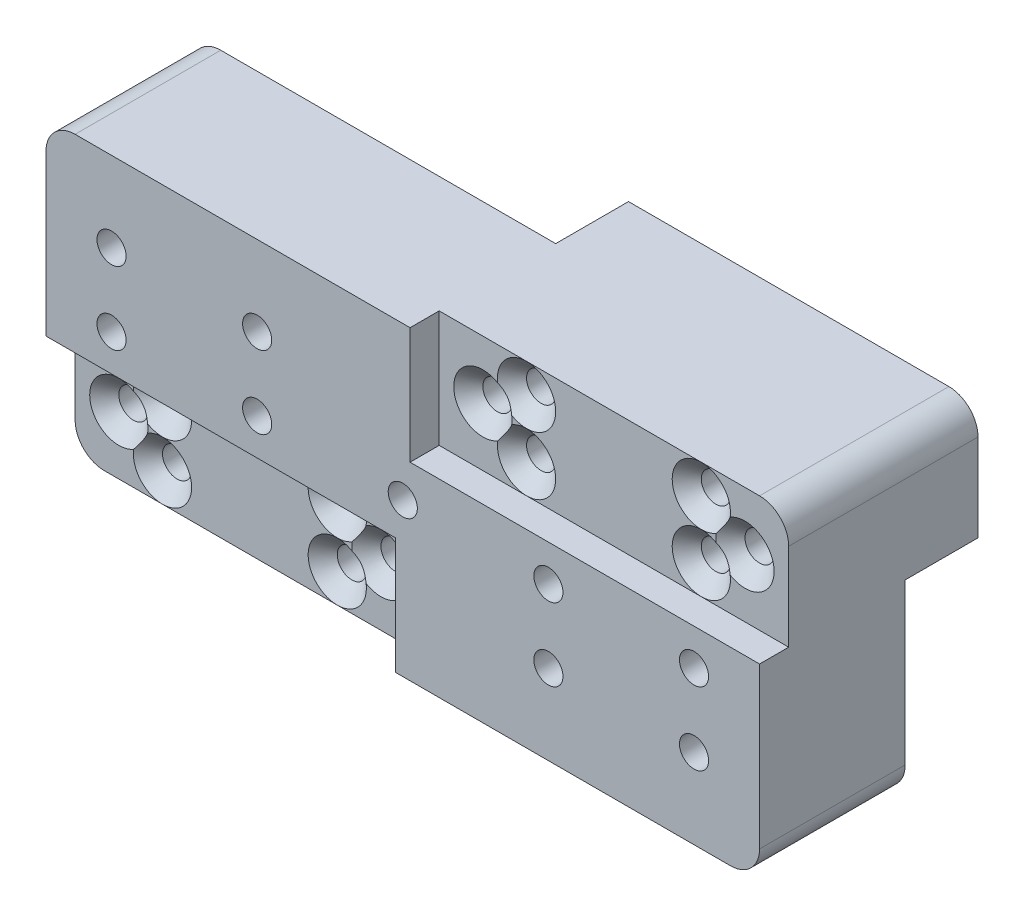
SolidWorks part; units mm, degrees
ref_plane "Front Plane" through (0, 0, 0) normal (0, 0, 1) x (1, 0, 0)
ref_plane "Top Plane" through (0, 0, 0) normal (0, 1, 0) x (1, 0, 0)
ref_plane "Right Plane" through (0, 0, 0) normal (1, 0, 0) x (0, 0, -1)
sketch "Sketch1" plane through (0, 0, 0) normal (0, 0, 1) x (1, 0, 0)
  line L0 (16.5, 10.5204) -> (16.5, 2.5204) construction
  line L1 (-20.5, -2.4796) -> (3.5, -2.4796)
  line L2 (-20.5, -2.4796) -> (-20.5, -10.4796)
  line L3 (-20.5, -10.4796) -> (3.5, -10.4796)
  line L4 (3.5, -2.4796) -> (3.5, -10.4796)
  line L5 (4.5, 10.5204) -> (28.5, 10.5204)
  line L6 (4.5, 10.5204) -> (4.5, 2.5204)
  line L7 (4.5, 2.5204) -> (28.5, 2.5204)
  line L8 (28.5, 10.5204) -> (28.5, 2.5204)
  line L9 (16.5, 6.5204) -> (4.5, 6.5204) construction
  line L10 (-8.5, -10.4796) -> (-8.5, -2.4796) construction
  line L11 (-8.5, -6.4796) -> (3.5, -6.4796) construction
  circle A0 centre (10.5, 8.5204) radius 1
  circle A1 centre (7.5, 6.5204) radius 1
  circle A2 centre (10.5, 4.5204) radius 1
  circle A3 centre (22.5, 4.5204) radius 1
  circle A4 centre (25.5, 6.5204) radius 1
  circle A5 centre (22.5, 8.5204) radius 1
  circle A6 centre (0.5, -6.4796) radius 1
  circle A7 centre (-14.5, -4.4796) radius 1
  circle A8 centre (-2.5, -8.4796) radius 1
  circle A10 centre (-17.5, -6.4796) radius 1
  circle A11 centre (-14.5, -8.4796) radius 1
  circle A12 centre (-2.5, -4.4796) radius 1
  dimension "D7" = 2
  dimension "D8" = 9
  dimension "D15" = 2
  dimension "D16" = 2
  dimension "D17" = 2
  dimension "D1" = 8
  dimension "D2" = 8
  dimension "D3" = 1
  dimension "D4" = 24
  dimension "D5" = 24
  dimension "D6" = 5
  dimension "D9" = 6
  dimension "D10" = 2
  dimension "D11" = 9
  dimension "D13" = 2
extrude "Boss-Extrude1" add sketch "Sketch1" along normal blind 5
sketch "Sketch2" plane through (0, 0, 5) normal (0, 0, 1) x (1, 0, 0)
  line L1 (-20.5, -10.4796) -> (28.5, -10.4796)
  line L2 (-20.5, -10.4796) -> (-20.5, 10.5204)
  line L3 (-20.5, 10.5204) -> (28.5, 10.5204)
  line L4 (-20.5, -2.4796) -> (-20.5, -10.4796)
  line L5 (-20.5, -10.4796) -> (3.5, -10.4796)
  line L6 (3.5, -10.4796) -> (3.5, -2.4796)
  line L7 (3.5, -2.4796) -> (-20.5, -2.4796)
  line L8 (-20.5, -2.4796) -> (-20.5, -10.4796)
  line L9 (-20.5, -10.4796) -> (3.5, -10.4796)
  line L10 (3.5, -10.4796) -> (3.5, -2.4796)
  line L11 (3.5, -2.4796) -> (-20.5, -2.4796)
  line L12 (4.5, 10.5204) -> (4.5, 2.5204)
  line L13 (4.5, 2.5204) -> (28.5, 2.5204)
  line L14 (28.5, 2.5204) -> (28.5, 10.5204)
  line L15 (28.5, 10.5204) -> (4.5, 10.5204)
  line L16 (4.5, 10.5204) -> (4.5, 2.5204)
  line L17 (4.5, 2.5204) -> (28.5, 2.5204)
  line L18 (28.5, 2.5204) -> (28.5, 10.5204)
  line L19 (28.5, 10.5204) -> (4.5, 10.5204)
  line L20 (28.5, -10.4796) -> (28.5, 10.5204)
  circle A0 centre (-14.5, -8.4796) radius 1 construction
  circle A1 centre (-17.5, -6.4796) radius 1 construction
  circle A2 centre (-14.5, -4.4796) radius 1 construction
  circle A3 centre (-2.5, -8.4796) radius 1 construction
  circle A5 centre (0.5, -6.4796) radius 1 construction
  circle A6 centre (7.5, 6.5204) radius 1 construction
  circle A7 centre (10.5, 8.5204) radius 1 construction
  circle A8 centre (10.5, 4.5204) radius 1 construction
  circle A9 centre (22.5, 8.5204) radius 1 construction
  circle A10 centre (25.5, 6.5204) radius 1 construction
  circle A11 centre (22.5, 4.5204) radius 1 construction
  circle A12 centre (22.5, 4.5204) radius 1
  circle A13 centre (25.5, 6.5204) radius 1
  circle A14 centre (22.5, 8.5204) radius 1
  circle A15 centre (10.5, 4.5204) radius 1
  circle A16 centre (10.5, 8.5204) radius 1
  circle A17 centre (7.5, 6.5204) radius 1
  circle A18 centre (0.5, -6.4796) radius 1
  circle A20 centre (-2.5, -8.4796) radius 1
  circle A21 centre (-14.5, -4.4796) radius 1
  circle A22 centre (-17.5, -6.4796) radius 1
  circle A23 centre (-14.5, -8.4796) radius 1
  circle A24 centre (-2.5, -4.4796) radius 1 construction
  circle A25 centre (-2.5, -4.4796) radius 1
  circle M9 centre (0.5, -6.4796) radius 1
  circle M10 centre (-14.5, -8.4796) radius 1
  circle M11 centre (-14.5, -4.4796) radius 1
  line M12 (-20.5, -2.4796) -> (-20.5, -10.4796)
  line M13 (-20.5, -10.4796) -> (3.5, -10.4796)
  line M14 (3.5, -10.4796) -> (3.5, -2.4796)
  line M15 (3.5, -2.4796) -> (-20.5, -2.4796)
  circle M16 centre (-17.5, -6.4796) radius 1
  circle M17 centre (-2.5, -8.4796) radius 1
  dimension "D1" = 0
  dimension "D2" = 0
extrude "Boss-Extrude2" add sketch "Sketch2" along normal blind 8 contours L1 L20 L17 L16 L3 L2 M15 M14 | L17 L18 L3 L16 A17 A16 A15 A14 A13 A12 | M15 M12 M13 M14 M10 M17 M16 M11 M9 region at (-8.5, -6.4796, 5) region at (4, 0.0204, 5) region at (16.5, 6.5204, 5)
extrude "Boss-Extrude3" add sketch "Sketch2<6>" along normal blind 10 contours L1 L20 L17 L16 L3 L2 M15 M14 region at (4, 0.0204, 5)
sketch "Sketch2<6>" plane through (0, 0, 5) normal (0, 0, 1) x (1, 0, 0) same geometry as "Sketch2"
chamfer "Chamfer1" distance 1 angle 45 12 edges at (11.5, 4.5204, 13) (8.5, 6.5204, 13) (-16.5, -6.4796, 13) (-13.5, -4.4796, 13) (-13.5, -8.4796, 13) (-1.5, -8.4796, 13) (1.5, -6.4796, 13) (26.5, 6.5204, 13) (23.5, 4.5204, 13) (23.5, 8.5204, 13) (11.5, 8.5204, 13) (-1.5, -4.4796, 13)
sketch "Sketch3" plane through (0, 0, 15) normal (0, 0, 1) x (1, 0, 0)
  line L0 (-20.5, 10.5204) -> (28.5, -10.4796) construction
  line L1 (4, 0.0204) -> (-20.5, 0.0204) construction
  line L2 (-20.5, 0.0204) -> (28.5, 0.0204) construction
  line L3 (-20.5, 5.0204) -> (4.5, 5.0204) construction
  line L4 (3.5, -4.9796) -> (28.5, -4.9796) construction
  line L5 (-16, 0.0204) -> (-16, 5.0204) construction
  line L6 (-6, 5.0204) -> (-6, 0.0204) construction
  line L7 (14, 0.0204) -> (14, -4.9796) construction
  line L8 (3.5, -10.4796) -> (28.5, -10.4796)
  line L9 (28.5, -10.4796) -> (28.5, 2.5204)
  line L10 (28.5, 2.5204) -> (4.5, 2.5204)
  line L11 (4.5, 2.5204) -> (4.5, 10.5204)
  line L12 (4.5, 10.5204) -> (-20.5, 10.5204)
  line L13 (-20.5, 10.5204) -> (-20.5, -2.4796)
  line L14 (-20.5, -2.4796) -> (3.5, -2.4796)
  line L15 (3.5, -2.4796) -> (3.5, -10.4796)
  line L16 (3.5, -10.4796) -> (28.5, -10.4796)
  line L17 (28.5, -10.4796) -> (28.5, 2.5204)
  line L18 (28.5, 2.5204) -> (4.5, 2.5204)
  line L19 (4.5, 2.5204) -> (4.5, 10.5204)
  line L20 (4.5, 10.5204) -> (-20.5, 10.5204)
  line L21 (-20.5, 10.5204) -> (-20.5, -2.4796)
  line L22 (-20.5, -2.4796) -> (3.5, -2.4796)
  line L23 (3.5, -2.4796) -> (3.5, -10.4796)
  line L24 (24, 0.0204) -> (24, -4.9796) construction
  circle A0 centre (4, 0.0204) radius 1
  circle A1 centre (14, 0.0204) radius 1
  circle A2 centre (24, 0.0204) radius 1
  circle A3 centre (-6, 0.0204) radius 1
  circle A4 centre (-16, 0.0204) radius 1
  circle A5 centre (-16, 5.0204) radius 1
  circle A6 centre (-6, 5.0204) radius 1
  circle A7 centre (14, -4.9796) radius 1
  circle A8 centre (24, -4.9796) radius 1
  dimension "D2" = 2
  dimension "D6" = 2
  dimension "D7" = 2
  dimension "D10" = 2
  dimension "D11" = 2
  dimension "D5" = 5
  dimension "6" = 5
  dimension "D1" = 0
  dimension "D3" = 3
  dimension "D4" = 3
fillet "Fillet1" radius 2 4 edges at (-20.5, -10.4796, 6.5) (28.5, -10.4796, 10) (28.5, 10.5204, 6.5) (-20.5, 10.5204, 10)
extrude "Cut-Extrude1" cut sketch "Sketch3" against normal blind 7 contours A4 | A5 | A6 | A3 | A0 | A1 | A7 | A2 | A8 region at (-16, 0.0204, 15)
